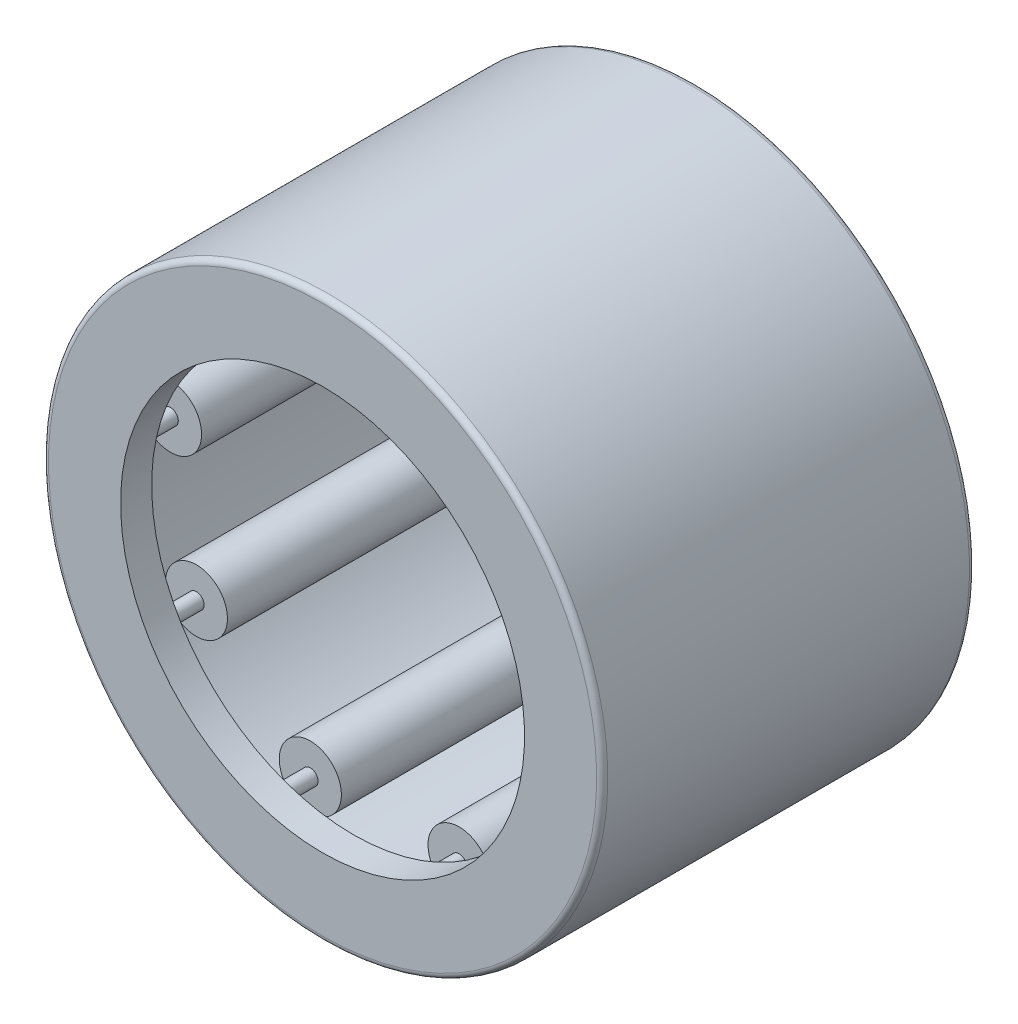
SolidWorks part; units mm, degrees
ref_plane "Front Plane" through (0, 0, 0) normal (0, 0, 1) x (1, 0, 0)
ref_plane "Top Plane" through (0, 0, 0) normal (0, 1, 0) x (1, 0, 0)
ref_plane "Right Plane" through (0, 0, 0) normal (1, 0, 0) x (0, 0, -1)
sketch "Sketch1" plane through (0, 0, 0) normal (1, 0, 0) x (0, 0, -1)
  line L0 (-4.7625, 0) -> (4.7625, 0) construction
  line L1 (0, 0) -> (0, 7.1438) construction
  line L2 (-4.7625, 0) -> (-4.7625, 7.1438) construction
  line L3 (-4.7625, 7.1438) -> (4.7625, 7.1438)
  line L4 (4.7625, 7.1438) -> (4.7625, 0) construction
  line L5 (4.7625, 0) -> (3.9688, 0) construction
  line L6 (3.9688, 0) -> (3.9688, 6.35) construction
  line L7 (3.9688, 6.35) -> (-3.9688, 6.35)
  line L8 (-3.9688, 6.35) -> (-3.9688, 0) construction
  line L9 (-3.9688, 0) -> (-4.7625, 0) construction
  line L10 (-4.7625, 7.1438) -> (-4.7625, 5.1594)
  line L11 (-4.7625, 5.1594) -> (-3.9688, 5.1594)
  line L12 (-3.9688, 5.1594) -> (-3.9688, 6.35)
  line L13 (3.9688, 7.1438) -> (3.9688, 6.35) construction
  line L14 (3.9688, 6.35) -> (3.9688, 5.1594)
  line L15 (3.9688, 5.1594) -> (4.7625, 5.1594)
  line L16 (4.7625, 5.1594) -> (4.7625, 7.1438)
  line L17 (3.9688, 6.35) -> (3.9688, 5.5563) construction
  line L18 (3.9688, 5.5563) -> (3.9688, 4.7625) construction
  point P5 (0, 4.7625)
  dimension "Width" = 9.525
  dimension "OD" = 14.2875
  dimension "Shaft Dia" = 9.525
revolve "Revolve1" add sketch "Sketch1" angle 360 about L0
sketch "Sketch2" plane through (0, 0, 0) normal (1, 0, 0) x (0, 0, -1)
  line L0 (3.9688, 6.35) -> (-3.9688, 6.35) construction
  line L1 (-3.175, 5.5563) -> (3.175, 5.5563) construction
  line L2 (-3.175, 5.5563) -> (-3.175, 6.35) construction
  line L3 (-3.175, 6.35) -> (3.175, 6.35)
  line L4 (3.175, 5.5563) -> (3.175, 6.35) construction
  line L5 (3.9688, 5.1594) -> (4.7625, 5.1594) construction
  line L6 (-3.9688, 5.5562) -> (-3.175, 5.5563) construction
  line L7 (3.175, 5.5563) -> (3.9688, 5.5562) construction
  line L8 (-4.7625, 5.1594) -> (-3.9688, 5.1594) construction
  line L9 (-3.175, 5.7547) -> (-3.175, 5.3578) construction
  line L10 (-3.9688, 5.5562) -> (-3.9688, 5.1594) construction
  line L11 (-3.175, 6.35) -> (-3.175, 5.7547)
  line L12 (3.175, 6.35) -> (3.175, 5.7547)
  line L13 (3.175, 5.7547) -> (-3.175, 5.7547)
  line L14 (0, 6.35) -> (0, 4.7625) construction
  line L15 (-3.9688, 5.1594) -> (-3.9688, 6.35) construction
  line L16 (-3.175, 5.3578) -> (-3.9688, 5.3578) construction
  line L17 (0, 0) -> (4.7625, 0) construction
  line L31 (4.7625, -7.1438) -> (4.7625, 7.1438) construction
  point P16 (0, 5.5563)
revolve "Revolve2" add sketch "Sketch2" angle 360 about L1
sketch "Sketch3" plane through (0, 0, 0) normal (1, 0, 0) x (0, 0, -1)
  line L0 (3.9688, 6.35) -> (3.9688, 5.1594) construction
  line L1 (-3.9688, 5.5562) -> (3.9688, 5.5562)
  line L2 (-3.9688, 5.5562) -> (-3.9688, 5.7547)
  line L3 (-3.9688, 5.7547) -> (3.9688, 5.7547)
  line L4 (3.9688, 5.5562) -> (3.9688, 5.7547)
  line L5 (0, 0) -> (4.7625, 0) construction
  line L6 (4.7625, -7.1438) -> (4.7625, 7.1438) construction
revolve "Revolve3" add sketch "Sketch3" angle 360 about L1
ref_axis "Axis1" through (0, 0, -4.7625) along (0, 0, 1)
pattern_circular "CirPattern1" count 9 every 40 about axis through (0, 0, -4.7625) along (0, 0, 1) of bodies 166 167
fillet "Fillet1" radius 0.1429 2 edges at (0, -7.1438, -4.7625) (0, -7.1438, 4.7625)
sketch "Sketch4" plane through (0, 0, 0) normal (1, 0, 0) x (0, 0, -1)
  line L1 (4.6196, 4.7625) -> (3.175, 4.7625)
  line L2 (4.6196, 4.7625) -> (4.6196, 5.1594)
  line L3 (4.6196, 5.1594) -> (3.175, 5.1594)
  line L4 (3.175, 4.7625) -> (3.175, 5.1594)
  line L5 (-4.7625, 5.1594) -> (-3.9688, 5.1594) construction
  line L6 (4.6196, -7.1438) -> (4.6196, 7.1437) construction
  line L7 (3.175, 6.35) -> (3.175, 5.7547) construction
revolve "Revolve4" [suppressed] add sketch "Sketch4" angle 360 about L0
sketch "Sketch5" plane through (0, 0, 0) normal (1, 0, 0) x (0, 0, -1)
  line L0 (-4.6196, 7.1438) -> (-4.6196, -7.1438) construction
  line L1 (-3.175, 4.7625) -> (-4.6196, 4.7625)
  line L2 (-3.175, 4.7625) -> (-3.175, 5.1594)
  line L3 (-3.175, 5.1594) -> (-4.6196, 5.1594)
  line L4 (-4.6196, 4.7625) -> (-4.6196, 5.1594)
  line L6 (-3.175, 6.35) -> (-3.175, 5.7547) construction
  line L7 (-4.7625, 5.1594) -> (-3.9688, 5.1594) construction
revolve "Revolve5" [suppressed] add sketch "Sketch5" angle 360 about L0
sketch "Front View" plane through (0, 0, 0) normal (0, 0, 1) x (1, 0, 0)
  circle A0 centre (0, 0) radius 4.7625 construction
  circle A1 centre (0, 0) radius 7.1438 construction
  dimension "OD" = 14.2875
  dimension "ID" = 9.525
sketch "Right View" plane through (0, 0, 0) normal (1, 0, 0) x (0, 0, -1)
  line L0 (-4.7625, 7.1438) -> (4.7625, 7.1438) construction
  dimension "Width" = 9.525
ref_axis "Center Axis 1" through (0, 0, -4.6196) along (0, 0, 1)
ref_plane "Contact Plane 1" through (0, 0, 4.7625) normal (0, 0, 1) x (1, 0, 0)
ref_plane "Contact Plane 2" through (0, 0, -4.7625) normal (0, 0, -1) x (-1, 0, 0)
equation "\"Rollers@CirPattern1\" = \"OD@Sketch1\"*16"
equation "\"D1@Fillet1\" = \"OD@Sketch1\"*.01"
equation "\"Angle@CirPattern1\"= 360 / \"Rollers@CirPattern1\""
equation "\"OD@Front View\"=\"OD@Sketch1\""
equation "\"ID@Front View\"=\"Shaft Dia@Sketch1\""
equation "\"Width@Right View\"=\"Width@Sketch1\""
